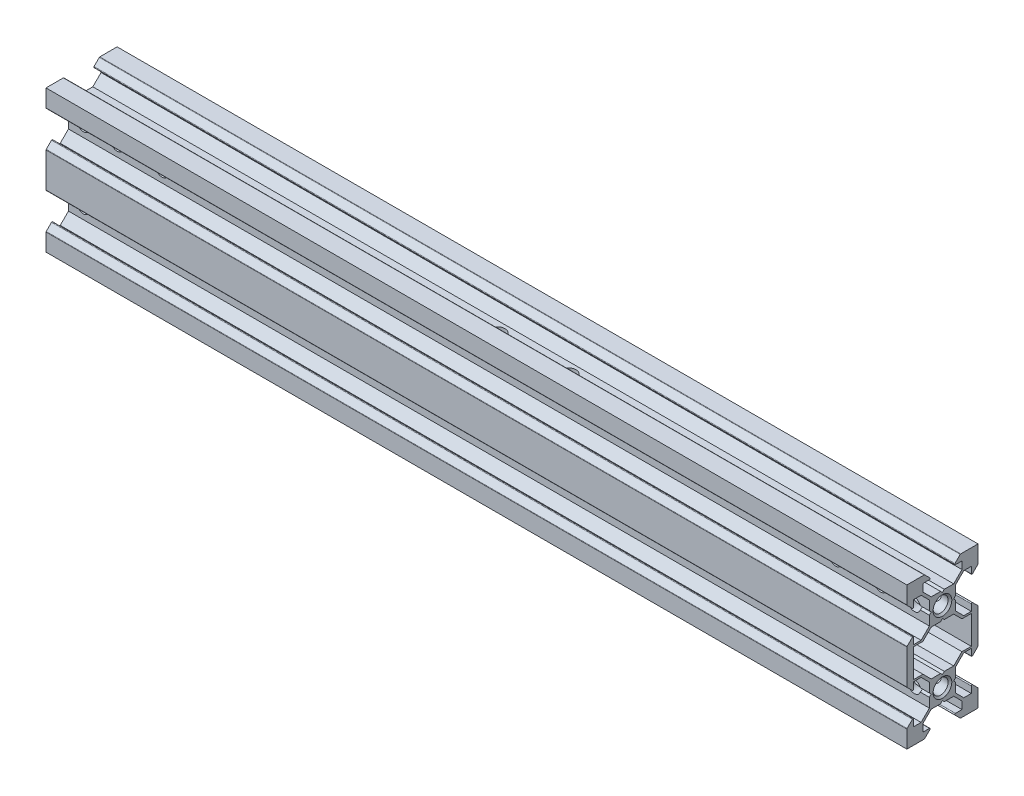
SolidWorks part; units mm, degrees
material "Alloy Steel"
ref_plane "Front Plane" through (0, 0, 0) normal (0, 0, 1) x (1, 0, 0)
ref_plane "Top Plane" through (0, 0, 0) normal (0, 1, 0) x (1, 0, 0)
ref_plane "Right Plane" through (0, 0, 0) normal (1, 0, 0) x (0, 0, -1)
sketch "Sketch2" plane through (0, 0, 0) normal (1, 0, 0) x (0, 0, -1)
  line L0 (0, 2) -> (0, 3) construction
  line L5 (0, 3) -> (-0.5, 3.5)
  line L6 (-0.5, 3.5) -> (-3.01, 3.5)
  line L7 (-3.01, 3.5) -> (-5.2091, 5.6991)
  line L8 (-5.2091, 5.6991) -> (-5.2091, 7.6991)
  line L9 (-5.2091, 7.6991) -> (-3.4791, 7.6991)
  line L10 (-3.4791, 7.6991) -> (-3.4791, 7.8991) construction
  line L11 (-3.4791, 7.8991) -> (-3.3377, 8.0405) construction
  line L12 (-3.3377, 8.0405) -> (-4.7378, 9.4406)
  line L13 (-4.7378, 9.4406) -> (-4.8792, 9.2992) construction
  line L14 (-4.8792, 9.2992) -> (-4.8792, 9.4992) construction
  line L15 (-4.8792, 9.4992) -> (-9.4992, 9.4992)
  line L16 (0, 0) -> (-9.4992, 9.4992) construction
  line L17 (0, 0) -> (-3, 0) construction
  line L18 (-9.4992, 4.8792) -> (-9.4992, 9.4992)
  line L19 (-8.0405, 3.3377) -> (-9.4406, 4.7378)
  line L20 (-7.6991, 5.2091) -> (-7.6991, 3.4791)
  line L21 (-5.6991, 5.2091) -> (-7.6991, 5.2091)
  line L22 (-3.5, 3.01) -> (-5.6991, 5.2091)
  line L23 (-3.5, 0.5) -> (-3.5, 3.01)
  line L24 (-3, 0) -> (-3.5, 0.5)
  line L25 (3, 0) -> (3.5, 0.5)
  line L26 (3.5, 0.5) -> (3.5, 3.01)
  line L27 (3.5, 3.01) -> (5.6991, 5.2091)
  line L28 (5.6991, 5.2091) -> (7.6991, 5.2091)
  line L29 (7.6991, 5.2091) -> (7.6991, 3.4791)
  line L30 (8.0405, 3.3377) -> (9.4406, 4.7378)
  line L31 (9.4992, 4.8792) -> (9.4992, 9.4992)
  line L32 (4.8792, 9.4992) -> (9.4992, 9.4992)
  line L33 (3.3377, 8.0405) -> (4.7378, 9.4406)
  line L34 (5.2091, 7.6991) -> (3.4791, 7.6991)
  line L35 (5.2091, 5.6991) -> (5.2091, 7.6991)
  line L36 (3.01, 3.5) -> (5.2091, 5.6991)
  line L37 (0.5, 3.5) -> (3.01, 3.5)
  line L38 (0, 3) -> (0.5, 3.5)
  line L39 (2, 0) -> (3, 0) construction
  line L40 (7.6991, 3.4791) -> (7.8991, 3.4791) construction
  line L41 (7.8991, 3.4791) -> (8.0405, 3.3377) construction
  line L42 (9.4406, 4.7378) -> (9.2992, 4.8792) construction
  line L43 (9.2992, 4.8792) -> (9.4992, 4.8792) construction
  line L44 (0, 0) -> (9.4992, 9.4992) construction
  line L45 (0, 0) -> (0, 3) construction
  line L46 (0, -3) -> (0.5, -3.5)
  line L47 (0.5, -3.5) -> (3.01, -3.5)
  line L48 (3.01, -3.5) -> (5.2091, -5.6991)
  line L49 (5.2091, -5.6991) -> (7.6991, -5.6991)
  line L50 (7.6991, -5.6991) -> (7.6991, -13.2992)
  line L51 (0, -15.9983) -> (0, -16.8134) construction
  line L52 (7.6991, -13.2992) -> (5.2091, -13.2992)
  line L53 (9.4992, -4.8792) -> (9.4992, -14.1192)
  line L54 (8.0405, -3.3377) -> (9.4406, -4.7378)
  line L55 (7.6991, -5.2091) -> (7.6991, -3.4791)
  line L56 (5.6991, -5.2091) -> (7.6991, -5.2091)
  line L57 (3.5, -3.01) -> (5.6991, -5.2091)
  line L58 (3.5, -0.5) -> (3.5, -3.01)
  line L59 (3, 0) -> (3.5, -0.5)
  line L60 (0, -2) -> (0, -3) construction
  line L61 (-7.6991, -13.2992) -> (-5.2091, -13.2992)
  line L62 (-7.6991, -5.6991) -> (-7.6991, -13.2992)
  line L63 (-5.2091, -5.6991) -> (-7.6991, -5.6991)
  line L65 (0, 0) -> (1.4142, -1.4142) construction
  line L66 (0, 0) -> (3, 0) construction
  line L67 (-3, 0) -> (-3.5, -0.5)
  line L68 (-3.5, -0.5) -> (-3.5, -3.01)
  line L69 (-3.5, -3.01) -> (-5.6991, -5.2091)
  line L70 (-5.6991, -5.2091) -> (-7.6991, -5.2091)
  line L71 (-7.6991, -5.2091) -> (-7.6991, -3.4791)
  line L72 (-8.0405, -3.3377) -> (-9.4406, -4.7378)
  line L73 (-9.4992, -4.8792) -> (-9.4992, -14.1192)
  line L78 (-3.01, -3.5) -> (-5.2091, -5.6991)
  line L79 (-0.5, -3.5) -> (-3.01, -3.5)
  line L80 (0, -3) -> (-0.5, -3.5)
  line L81 (-2, 0) -> (-3, 0) construction
  line L82 (-7.6991, -3.4791) -> (-7.8991, -3.4791) construction
  line L83 (-7.8991, -3.4791) -> (-8.0405, -3.3377) construction
  line L84 (-9.4406, -4.7378) -> (-9.2992, -4.8792) construction
  line L85 (-9.2992, -4.8792) -> (-9.4992, -4.8792) construction
  line L86 (0, 0) -> (-1.4142, -1.4142) construction
  line L87 (0, 0) -> (0, -3) construction
  line L89 (-4.8792, -28.4975) -> (-9.4992, -28.4975)
  line L90 (-3.3377, -27.0389) -> (-4.7378, -28.4389)
  line L91 (-5.2091, -26.6974) -> (-3.4791, -26.6974)
  line L92 (-5.2091, -24.6974) -> (-5.2091, -26.6974)
  line L93 (-9.4992, -23.8775) -> (-9.4992, -28.4975)
  line L94 (-8.0405, -22.336) -> (-9.4406, -23.7361)
  line L95 (-7.6991, -24.2074) -> (-7.6991, -22.4774)
  line L96 (-5.6991, -24.2074) -> (-7.6991, -24.2074)
  line L97 (5.2091, -26.6974) -> (3.4791, -26.6974)
  line L98 (3.3377, -27.0389) -> (4.7378, -28.4389)
  line L99 (4.8792, -28.4975) -> (9.4992, -28.4975)
  line L100 (9.4992, -23.8775) -> (9.4992, -28.4975)
  line L101 (8.0405, -22.336) -> (9.4406, -23.7361)
  line L102 (7.6991, -24.2074) -> (7.6991, -22.4774)
  line L103 (5.6991, -24.2074) -> (7.6991, -24.2074)
  line L104 (5.2091, -24.6974) -> (5.2091, -26.6974)
  line L105 (3.01, -22.4983) -> (5.2091, -24.6974)
  line L106 (3.5, -22.0083) -> (5.6991, -24.2074)
  line L107 (-3.5, -22.0083) -> (-5.6991, -24.2074)
  line L108 (-3.01, -22.4983) -> (-5.2091, -24.6974)
  line L109 (-0.5, -22.4983) -> (-3.01, -22.4983)
  line L110 (0, -21.9983) -> (0.5, -22.4983)
  line L111 (0, -21.9983) -> (-0.5, -22.4983)
  line L112 (0.5, -22.4983) -> (3.01, -22.4983)
  line L113 (3.5, -19.4983) -> (3.5, -22.0083)
  line L114 (-3.5, -19.4983) -> (-3.5, -22.0083)
  line L115 (-3, -18.9983) -> (-3.5, -19.4983)
  line L116 (-3, -18.9983) -> (-3.5, -18.4983)
  line L117 (3, -18.9983) -> (3.5, -19.4983)
  line L118 (3, -18.9983) -> (3.5, -18.4983)
  line L119 (3.5, -18.4983) -> (3.5, -15.9883)
  line L120 (3.01, -15.4983) -> (5.2091, -13.2992)
  line L121 (3.5, -15.9883) -> (5.6991, -13.7892)
  line L122 (5.6991, -13.7892) -> (7.6991, -13.7892)
  line L123 (7.6991, -13.7892) -> (7.6991, -15.5192)
  line L124 (8.0405, -15.6607) -> (9.4406, -14.2606)
  line L128 (-5.6991, -13.7892) -> (-7.6991, -13.7892)
  line L129 (-7.6991, -13.7892) -> (-7.6991, -15.5192)
  line L130 (-8.0405, -15.6607) -> (-9.4406, -14.2606)
  line L134 (-3.01, -15.4983) -> (-5.2091, -13.2992)
  line L135 (-3.5, -15.9883) -> (-5.6991, -13.7892)
  line L136 (-3.5, -18.4983) -> (-3.5, -15.9883)
  line L137 (-0.5, -15.4983) -> (-3.01, -15.4983)
  line L138 (0, -15.9983) -> (-0.5, -15.4983)
  line L139 (0, -15.9983) -> (0.5, -15.4983)
  line L140 (0.5, -15.4983) -> (3.01, -15.4983)
  circle A0 centre (0, 0) radius 2
  arc A1 (-3.3377, 8.0405) -> (-3.4791, 7.6991) centre (-3.4791, 7.8991) cw
  arc A2 (-4.7378, 9.4406) -> (-4.8792, 9.4992) centre (-4.8792, 9.2992) ccw
  arc A3 (-9.4406, 4.7378) -> (-9.4992, 4.8792) centre (-9.2992, 4.8792) cw
  arc A4 (-8.0405, 3.3377) -> (-7.6991, 3.4791) centre (-7.8991, 3.4791) ccw
  arc A5 (8.0405, 3.3377) -> (7.6991, 3.4791) centre (7.8991, 3.4791) cw
  arc A6 (9.4406, 4.7378) -> (9.4992, 4.8792) centre (9.2992, 4.8792) ccw
  arc A7 (4.7378, 9.4406) -> (4.8792, 9.4992) centre (4.8792, 9.2992) cw
  arc A8 (3.3377, 8.0405) -> (3.4791, 7.6991) centre (3.4791, 7.8991) ccw
  arc A11 (9.4406, -4.7378) -> (9.4992, -4.8792) centre (9.2992, -4.8792) cw
  arc A12 (8.0405, -3.3377) -> (7.6991, -3.4791) centre (7.8991, -3.4791) ccw
  arc A13 (-8.0405, -3.3377) -> (-7.6991, -3.4791) centre (-7.8991, -3.4791) cw
  arc A14 (-9.4406, -4.7378) -> (-9.4992, -4.8792) centre (-9.2992, -4.8792) ccw
  arc A17 (-4.7378, -28.4389) -> (-4.8792, -28.4975) centre (-4.8792, -28.2975) cw
  arc A18 (-3.3377, -27.0389) -> (-3.4791, -26.6974) centre (-3.4791, -26.8974) ccw
  arc A19 (-9.4406, -23.7361) -> (-9.4992, -23.8775) centre (-9.2992, -23.8775) ccw
  arc A20 (-8.0405, -22.336) -> (-7.6991, -22.4774) centre (-7.8991, -22.4774) cw
  arc A21 (3.3377, -27.0389) -> (3.4791, -26.6974) centre (3.4791, -26.8974) cw
  arc A22 (4.7378, -28.4389) -> (4.8792, -28.4975) centre (4.8792, -28.2975) ccw
  arc A23 (9.4406, -23.7361) -> (9.4992, -23.8775) centre (9.2992, -23.8775) cw
  arc A24 (8.0405, -22.336) -> (7.6991, -22.4774) centre (7.8991, -22.4774) ccw
  arc A25 (8.0405, -15.6607) -> (7.6991, -15.5192) centre (7.8991, -15.5192) cw
  arc A26 (9.4406, -14.2606) -> (9.4992, -14.1192) centre (9.2992, -14.1192) ccw
  arc A30 (-8.0405, -15.6607) -> (-7.6991, -15.5192) centre (-7.8991, -15.5192) ccw
  arc A31 (-9.4406, -14.2606) -> (-9.4992, -14.1192) centre (-9.2992, -14.1192) cw
  circle A33 centre (0, -18.9983) radius 2
  point P0 (0, 0)
  point P22 (0, 0)
  point P64 (0, 0)
  point P93 (0, 0)
  point P122 (0, 0)
extrude "Main Body" add sketch "Sketch2" along normal blind 115 and the other way blind 115 contours L78 L79 L80 L46 L47 L48 L53 A11 L54 A12 L55 L56 L57 L58 L59 L25 L26 L27 L28 L29 A5 L30 A6 L31 L32 A7 L33 A8 L34 L35 L36 L37 L38 L5 L6 L7 L8 L9 A1 L12 A2 region at (0, 2.9496, -0.5504)
chamfer "Chamfer1" distance 0.5 angle 45 1 edges at (115, 0, -2)
chamfer "Chamfer2" distance 0.5 angle 45 3 edges at (-115, 0, -2) (115, -18.9983, -2) (-115, -18.9983, -2)
sketch "Sketch3" plane through (0, 0, 0) normal (0, 0, 1) x (1, 0, 0)
  line L0 (-115, 0) -> (115, 0) construction
  line L1 (-115, -18.9983) -> (115, -18.9983) construction
  line L2 (-115, -0.5) -> (-115, -3.01) construction
  line L3 (-115, -18.4983) -> (-115, -15.9883) construction
  line L4 (0, 0) -> (0, -12.038) construction
  line L5 (-115, -4.8792) -> (-115, -14.1192) construction
  circle A0 centre (-111, 0) radius 1.65
  circle A1 centre (-111, -18.9983) radius 1.65
  circle A4 centre (-102, 0) radius 1.65
  circle A5 centre (-90, 0) radius 1.65
  circle A6 centre (111, -18.9983) radius 1.65
  circle A7 centre (111, 0) radius 1.65
  circle A8 centre (102, 0) radius 1.65
  circle A9 centre (90, 0) radius 1.65
  dimension "D1" = 3.3
  dimension "D3" = 3.3
  dimension "D9" = 3.3
  dimension "D10" = 3.3
  dimension "D2" = 4
  dimension "D4" = 4
  dimension "D11" = 13
  dimension "D12" = 25
extrude "Side Holes" cut sketch "Sketch3" against normal through all both and the other way through all
sketch "Sketch4" plane through (0, 0, 0) normal (0, 1, 0) x (1, 0, 0)
  line L0 (-115, 0) -> (115, 0) construction
  line L1 (-115, -0.5) -> (-115, -3.01) construction
  circle A0 centre (-4, 0) radius 2.1
  circle A1 centre (15, 0) radius 2.1
  dimension "D1" = 4.2
  dimension "D2" = 4.2
  dimension "D3" = 19
  dimension "D4" = 130
extrude "Top Holes" cut sketch "Sketch4" along normal blind 10 and the other way blind 10
